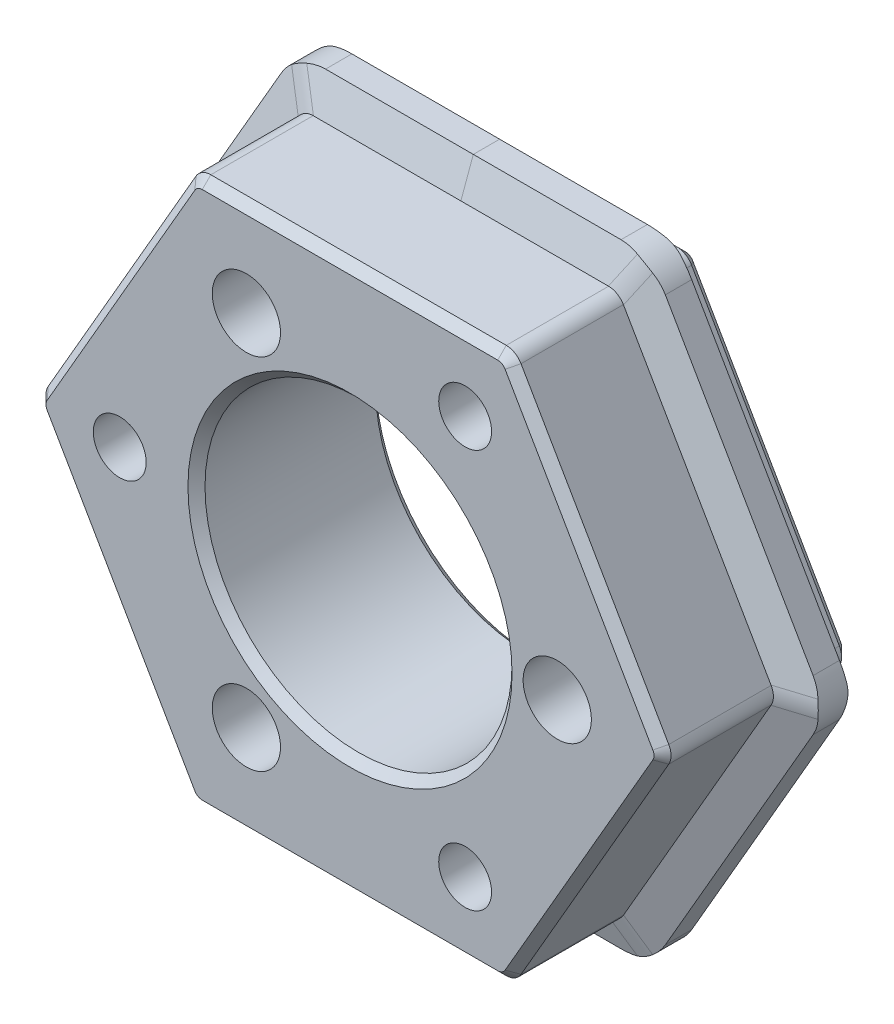
SolidWorks part; units mm, degrees
material "6061 合金"
ref_plane "前视基准面" through (0, 0, 0) normal (0, 0, 1) x (1, 0, 0)
ref_plane "上视基准面" through (0, 0, 0) normal (0, 1, 0) x (1, 0, 0)
ref_plane "右视基准面" through (0, 0, 0) normal (1, 0, 0) x (0, 0, -1)
other "Configuration Table"
sketch "草图2" plane through (0, 0, 0) normal (0, 0, 1) x (1, 0, 0)
  line L1 (9.2376, 16) -> (-9.2376, 16)
  line L2 (-9.2376, 16) -> (-18.4752, 0)
  line L3 (-18.4752, 0) -> (-9.2376, -16)
  line L4 (-9.2376, -16) -> (9.2376, -16)
  line L5 (9.2376, -16) -> (18.4752, 0)
  line L6 (18.4752, 0) -> (9.2376, 16)
  circle A0 centre (0, 0) radius 16 construction
  dimension "D1" = 32
extrude "凸台-拉伸1" add sketch "草图2" along normal mid plane 11
hole_wizard "M3 六角圆柱头螺钉的柱形沉头孔1" positions "草图4" profile "草图5" counterbore size "M3" standard "GB" end condition through all
sketch "草图4" plane through (0, 0, -5.5) normal (0, 0, -1) x (-1, 0, 0)
  line L0 (-18.4752, 0) -> (0, 0) construction
  line L1 (0, 0) -> (-6.75, 11.6913) construction
  circle A0 centre (0, 0) radius 13.5
  point P0 (-6.75, 11.6913)
  point P24 (13.5, 0)
  point P25 (-6.75, -11.6913)
  dimension "D1" = 27
  dimension "D2" = 60
  dimension "D3" = 3
sketch "草图5" plane through (6.75, 11.6913, -5.5) normal (1, 0, 0) x (0, 1, 0)
  line L0 (0, 0) -> (0, 11)
  line L1 (0, 11) -> (1.55, 11)
  line L3 (1.55, 11) -> (1.55, 3.1)
  line L4 (1.55, 3.1) -> (3, 3.1)
  line L5 (3, 3.1) -> (3, 0)
  line L7 (3, 0) -> (0, 0)
  line L11 (0, -6.35) -> (0, 107.95) construction
  dimension "通孔孔直径" = 3.1
  dimension "通孔孔深度" = 11
  dimension "柱形沉头孔直径" = 6
  dimension "柱形沉头孔深度" = 3.1
hole_wizard "Ø4.0mm 暗销孔1" positions "草图6" profile "草图7" hole size "Ø4.0" standard "GB"
sketch "草图6" plane through (0, 0, 5.5) normal (0, 0, 1) x (1, 0, 0)
  line L0 (-23.5778, 0) -> (0, 0) construction
  line L1 (0, 0) -> (-6.075, 10.5222) construction
  circle A0 centre (0, 0) radius 12.15
  point P0 (-6.075, 10.5222)
  point P19 (12.15, 0)
  point P20 (-6.075, -10.5222)
  dimension "D1" = 24.3
  dimension "D2" = 60
  dimension "D3" = 3
sketch "草图7" plane through (-6.075, 10.5222, 5.5) normal (1, 0, 0) x (0, -1, 0)
  line L0 (0, 0) -> (0, 4.2017)
  line L1 (0, 4.2017) -> (2, 3)
  line L2 (2, 3) -> (2, 0)
  line L5 (2, 0) -> (0, 0)
  line L10 (0, 4.2017) -> (-2, 3) construction
  line L11 (0, -6.35) -> (0, 107.95) construction
  dimension "孔直径" = 4
  dimension "孔深度" = 3
  dimension "导头角度" = 118
sketch "草图8" plane through (0, 0, 5.5) normal (0, 0, 1) x (1, 0, 0)
  circle A0 centre (0, 0) radius 9
  dimension "D1" = 18
extrude "切除-拉伸1" cut sketch "草图8" against normal through all
ref_plane "基准面1" through (0, 0, -2.5) normal (0, 0, -1) x (-1, 0, 0)
sketch "草图10" plane through (0, 0, -2.5) normal (0, 0, -1) x (-1, 0, 0)
  line L6 (-9.2376, 16) -> (-18.4752, 0)
  line L7 (-18.4752, 0) -> (-9.2376, -16)
  line L8 (-9.2376, -16) -> (9.2376, -16)
  line L9 (9.2376, -16) -> (18.4752, 0)
  line L10 (18.4752, 0) -> (9.2376, 16)
  line L11 (9.2376, 16) -> (-9.2376, 16)
  line L12 (-9.2376, 16) -> (-18.4752, 0)
  line L13 (-18.4752, 0) -> (-9.2376, -16)
  line L14 (-9.2376, -16) -> (9.2376, -16)
  line L15 (9.2376, -16) -> (18.4752, 0)
  line L16 (18.4752, 0) -> (9.2376, 16)
  line L17 (9.2376, 16) -> (-9.2376, 16)
  dimension "D1" = 0
sketch "草图11" plane through (0, 0, 0) normal (1, 0, 0) x (0, 0, -1)
  line L0 (2.5, 16) -> (2.5, 0) construction
  line L1 (2.5, 16) -> (2.5, -0.3955) construction
  line L2 (1, 16) -> (1.7279, 18)
  line L3 (-5.5, 16) -> (5.5, 16) construction
  line L4 (1.7279, 18) -> (3.2721, 18)
  line L5 (3.2721, 18) -> (4, 16)
  line L6 (4, 16) -> (1, 16)
  dimension "D1" = 2
  dimension "D2" = 40
  dimension "D3" = 3
sweep "扫描1" add profiles "草图11" path "草图10"
fillet "圆角1" radius 3 18 edges at (10.3923, 18, -2.5) (20.7846, 0, -2.5) (10.3923, -18, -2.5) (-10.3923, -18, -2.5) (-20.7846, 0, -2.5) (-10.3923, 18, -2.5) (-9.815, -17, -3.636) (9.815, -17, -3.636) (19.6299, 0, -3.636) (9.815, 17, -3.636) (-9.815, 17, -3.636) (-19.6299, 0, -3.636) (9.815, 17, -1.364) (-9.815, 17, -1.364) (-19.6299, 0, -1.364) (-9.815, -17, -1.364) (9.815, -17, -1.364) (19.6299, 0, -1.364)
fillet "圆角2" radius 1 12 edges at (-9.2376, -16, 2.2265) (9.2376, -16, 2.2265) (18.4752, 0, 2.2265) (9.2376, 16, 2.2265) (-9.2376, 16, 2.2265) (-18.4752, 0, 2.2265) (-18.4752, 0, -4.7265) (-9.2376, -16, -4.7265) (9.2376, -16, -4.7265) (18.4752, 0, -4.7265) (9.2376, 16, -4.7265) (-9.2376, 16, -4.7265)
chamfer "倒角1" distance 0.5 angle 45 26 edges at (9, 0, 5.5) (9, 0, -5.5) (-13.8564, 8, 5.5) (-18.3205, 0, 5.5) (-9.1603, 15.866, 5.5) (-13.8564, -8, 5.5) (0, 16, 5.5) (-9.1603, -15.866, 5.5) (9.1603, 15.866, 5.5) (0, -16, 5.5) (13.8564, 8, 5.5) (9.1603, -15.866, 5.5) (18.3205, 0, 5.5) (13.8564, -8, 5.5) (0, 16, -5.5) (-9.1603, 15.866, -5.5) (9.1603, 15.866, -5.5) (-13.8564, 8, -5.5) (13.8564, 8, -5.5) (-18.3205, 0, -5.5) (18.3205, 0, -5.5) (-13.8564, -8, -5.5) (13.8564, -8, -5.5) (-9.1603, -15.866, -5.5) (9.1603, -15.866, -5.5) (0, -16, -5.5)
